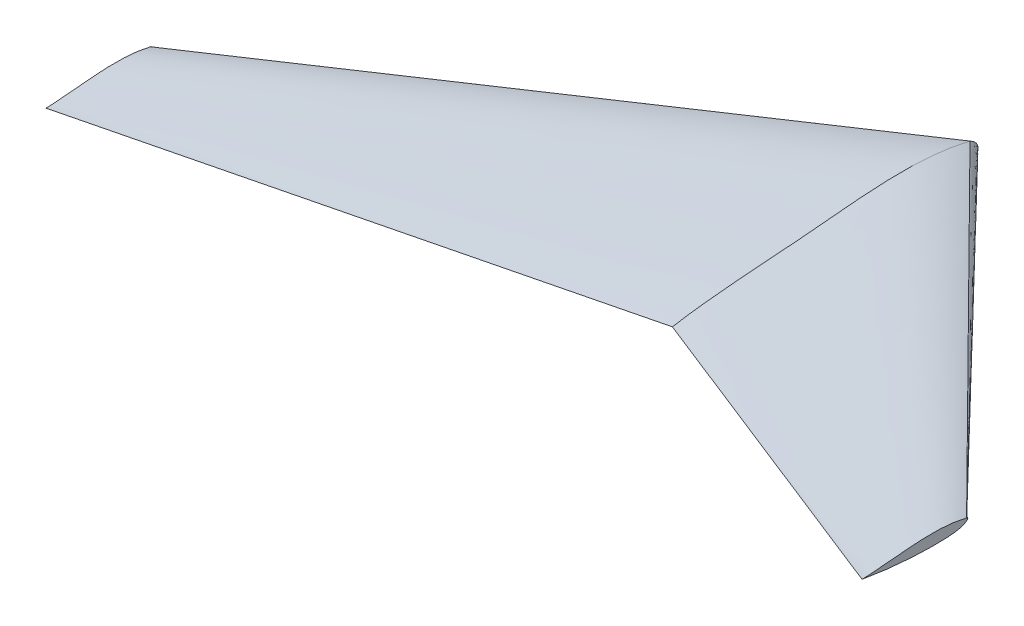
SolidWorks part; units mm, degrees
ref_plane "Front Plane" through (0, 0, 0) normal (0, 0, 1) x (1, 0, 0)
ref_plane "Top Plane" through (0, 0, 0) normal (0, 1, 0) x (1, 0, 0)
ref_plane "Right Plane" through (0, 0, 0) normal (1, 0, 0) x (0, 0, -1)
sketch "Sketch2" plane through (0, 0, 0) normal (0, 1, 0) x (1, 0, 0)
  line L0 (0, -6122.228) -> (0, 2040.7427)
  line L1 (0, 0) -> (-18096.1342, 0) construction
  line L2 (0, 0) -> (-21640.8, -16307.5125) construction
  line L3 (-21640.8, -18450.2946) -> (-21640.8, -15593.2518)
  line L4 (-21640.8, -15593.2518) -> (0, 2040.7427)
  line L5 (-21640.8, -18450.2946) -> (0, -6122.228)
  line L6 (-9083.802, -5361.1886) -> (-9083.802, -6845.1358) construction
  line L7 (-9083.802, -6845.1358) -> (-9083.802, -11296.9774) construction
  line L8 (-9083.802, -6845.1358) -> (0, -6845.1358) construction
  line L9 (0, 408.1485) -> (-18440.4, -13713.752)
  line L10 (0, -35661.6) -> (-6061.5652, -41119.4578) construction
  line L11 (0, -35661.6) -> (-8167.6786, -35661.6) construction
  line L12 (0, -34539.0879) -> (0, -39029.1363)
  line L13 (-6061.5652, -42298.0954) -> (-6061.5652, -40726.5786)
  line L14 (-6061.5652, -40726.5786) -> (0, -34539.0879)
  line L15 (0, -39029.1363) -> (-6061.5652, -42298.0954)
  line L16 (-2544.3607, -37136.3062) -> (-2544.3607, -37952.5526) construction
  line L17 (-2544.3607, -37952.5526) -> (-2544.3607, -40401.292) construction
  line L18 (-2544.3607, -37952.5526) -> (0, -37952.5526) construction
  line L19 (-18440.4, -13713.752) -> (-18440.4, -15898.787)
  line L20 (-18440.4, -15898.787) -> (0, -4489.6339)
  line L21 (0, 408.1485) -> (0, -4489.6339) construction
  line L22 (0, -4489.6339) -> (0, 408.1485) construction
  line L23 (0, 408.1485) -> (0, -2040.7427) construction
  line L24 (0, 408.1485) -> (0, -4489.6339) construction
  line L25 (0, -2040.7427) -> (-18440.4, -14806.2695) construction
  line L26 (0, 408.1485) -> (-21640.8, -16164.6603) construction
  line L27 (-6975.7046, -4933.9377) -> (-6975.7046, -6869.7347) construction
  line L28 (-6975.7046, -6869.7347) -> (-6975.7046, -8805.5317) construction
  line L29 (-6975.7046, -6869.7347) -> (0, -6869.7347) construction
  line L30 (-6061.5652, -41661.6311) -> (0, -37210.6667) construction
  dimension "Wing Sweep" = 37
  dimension "Half Span" = 21640.8
  dimension "Wing Root" = 8162.9707
  dimension "D4" = 2040.7427
  dimension "Wing Tip" = 2857.0428
  dimension "D6" = 714.2607
  dimension "Wing YBar" = 9083.802
  dimension "Tail Sweep" = 42
  dimension "Tail Root" = 4490.0484
  dimension "D10" = 1122.5121
  dimension "Tail Tip" = 1571.5168
  dimension "D12" = 392.8792
  dimension "D13" = 6061.5652
  dimension "Tail Ybar" = 2544.3607
  dimension "First Spar" = 1632.5941
  dimension "Second Spar" = 6530.3766
  dimension "Fuel Tip" = 2185.035
  dimension "Tip Spar" = 571.4086
  dimension "Fuel Ybar" = 6975.7046
  dimension "Fuel Tank Length" = 18440.4
  dimension "Tail Arm" = 35661.6
  dimension "D2" = 2671.5788
  dimension "D3" = 935.0525
sketch "Sketch4" plane through (0, 0, 0) normal (0, 1, 0) x (1, 0, 0)
  line L0 (0, 17538.8642) -> (0, -40677.9358) construction
  line L1 (-2194.56, 17538.8642) -> (2194.56, 17538.8642) construction
  line L2 (-2194.56, 10955.1842) -> (-2194.56, -31899.6958)
  line L3 (-2194.56, -40677.9358) -> (2194.56, -40677.9358) construction
  line L4 (2194.56, 10955.1842) -> (2194.56, -31899.6958)
  line L5 (0, -6122.228) -> (0, 2040.7427) construction
  line L6 (-9083.802, -6845.1358) -> (0, -6845.1358) construction
  line L7 (-2544.3607, -37952.5526) -> (0, -37952.5526) construction
  line L8 (0, 0) -> (-21640.8, -16307.5125) construction
  line L9 (-21640.8, -15593.2518) -> (0, 2040.7427) construction
  line L10 (-8474.964, 1555.5245) -> (-5807.964, 1555.5245)
  line L11 (-8474.964, 1555.5245) -> (-8474.964, -5453.2245)
  line L12 (-8474.964, -5453.2245) -> (-5807.964, -5453.2245)
  line L13 (-5807.964, 1555.5245) -> (-5807.964, -5453.2245)
  line L14 (2194.56, 10955.1842) -> (-2194.56, 10955.1842)
  arc A0 (-2194.56, -31899.6958) -> (2194.56, -31899.6958) centre (0, -31899.6958) ccw construction
  spline S0 degree 2 poles (-2194.56, 10955.1842) (-2319.3121, 14550.827) (0, 17538.8642) knots 0 0 0 1 1 1 construction
  spline S1 degree 2 poles (2194.56, 10955.1842) (2319.3121, 14550.827) (0, 17538.8642) knots 0 0 0 1 1 1 construction
  spline S2 degree 3 poles (-2194.56, -31899.6958) (-2185.0252, -17343.0176) (-1882.3736, -55849.4008) (-475.0937, -22625.7195) (0, -39029.1363) knots 0 0 0 0 0.566127 1 1 1 1 construction
  spline S3 degree 3 poles (2194.56, -31899.6958) (2185.0252, -17343.0176) (1882.3736, -55849.4008) (475.0937, -22625.7195) (0, -39029.1363) knots 0 0 0 0 0.566127 1 1 1 1 construction
  spline S4 degree 2 poles (-2194.56, -31899.6958) (-4104.2514, -24790.3016) (0, -27753.3552) knots 0 0 0 1 1 1
  spline S5 degree 2 poles (2194.56, -31899.6958) (4104.2514, -24790.3016) (0, -27753.3552) knots 0 0 0 1 1 1
  point P6 (0, 10955.1842)
  point P7 (0, -31899.6958)
  point P8 (0, -6845.1358)
  point P15 (0, -34094.2558)
  point P28 (-7141.464, 1555.5245)
  point P29 (-7141.464, -3778.4755)
  point P35 (-7141.464, -5381.4791)
  point P44 (-7141.464, -1247.9751)
  dimension "Fuse Length" = 58216.8
  dimension "Fuse Dia" = 4389.12
  dimension "D3" = 6583.68
  dimension "D4" = 8778.24
  dimension "D6" = 7141.464
  dimension "Engine Dia" = 2667
  dimension "Engine Length" = 7008.749
  dimension "D9" = 5334
  dimension "D10" = 2803.4996
  dimension "D11" = 5597.1607
  dimension "D2" = 24384
ref_plane "Plane1" through (0, 609.6, 0) normal (0, 1, 0) x (1, 0, 0)
sketch "Sketch10" plane through (0, 0, 0) normal (0, 1, 0) x (1, 0, 0)
  line L0 (-21640.8, -15593.2518) -> (-2194.56, 252.5066)
  line L1 (-2194.56, 10955.1842) -> (-2194.56, -31899.6958) construction
  line L2 (-21640.8, -15593.2518) -> (-21640.8, -18450.2946)
  line L3 (-21640.8, -18450.2946) -> (-7141.464, -10190.49)
  line L4 (-7141.464, -10190.49) -> (-2194.56, -10190.49)
  line L5 (-21640.8, -18450.2946) -> (0, -6122.228) construction
  line L6 (-21640.8, -15593.2518) -> (0, 2040.7427) construction
  line L7 (-2194.56, -10190.49) -> (-2194.56, 252.5066) construction
  line L9 (0, 271.2873) -> (0, -10190.49)
  line L10 (0, -10190.49) -> (-2194.56, -10190.49)
  line L11 (0, -6122.228) -> (0, 2040.7427) construction
  line L12 (-2194.56, 252.5066) -> (0, 2040.7427)
  line L13 (0, 2040.7427) -> (0, 271.2873)
ref_plane "Plane4" through (17265.894, 0, 16914.5049) normal (0.7143, 0, 0.6998) x (0.6998, 0, -0.7143)
ref_plane "Plane2" through (-6061.5652, 0, 0) normal (1, 0, 0) x (0, 0, -1)
sketch "Sketch11" plane through (0, 0, 0) normal (1, 0, 0) x (0, 0, -1)
  line L0 (-31394.1382, -352.4096) -> (-30857.4716, -352.4096) construction
  line L1 (-34539.0879, 0) -> (-39029.1363, 0) construction
  spline S0 degree 3 poles (-39051.8309, 0) (-38403.1581, 109.7274) (-36924.0487, 165.2873) (-35448.5779, 379.0643) (-34630.3278, 179.2815) knots 0 0 0 0 0.443797 1 1 1 1
  spline S1 degree 3 poles (-39051.8309, 0) (-38190.4109, -219.3036) (-37292.2896, -199.7787) (-36415.6545, -314.689) knots 0 0 0 0 1 1 1 1
  spline S2 degree 3 poles (-36415.6545, -314.689) (-35966.3296, -355.4965) (-35302.3779, -490.2862) (-34639.9796, -191.5367) (-34412.4231, 59.404) (-34630.3278, 179.2815) knots 0 0 0 0 0.638862 0.803347 1 1 1 1
sketch "Sketch12" plane through (17265.894, 0, 16914.5049) normal (0.7143, 0, 0.6998) x (0.6998, 0, -0.7143)
  line L0 (-24430.9437, -230.124) -> (-33334.4448, 1320.3427)
  line L1 (-24430.9437, 230.124) -> (-33334.4448, 1481.4295)
  line L2 (-24430.9437, 230.124) -> (-24430.9437, -230.124) construction
  line L3 (-33334.4448, 1481.4295) -> (-33334.4448, 1320.3427) construction
  line L4 (-24672.5966, 0) -> (-27880.0105, 0) construction
  line L5 (-33334.4448, 1481.4295) -> (-29601.6778, 1481.4295) construction
  point P1 (-24430.9437, 0)
  dimension "D2" = 460.248
  dimension "D1" = 161.0868
  dimension "D3" = 8
sketch "Sketch13" plane through (-6061.5652, 0, 0) normal (1, 0, 0) x (0, 0, -1)
  line L0 (-34331.3091, -72.3608) -> (-33794.6424, -72.3608) construction
  spline S0 degree 2 poles (-40724.5294, 1404.4596) (-40730.5109, 1415.5035) (-40742.886, 1417.5169) knots 0 0 0 1 1 1
  spline S1 degree 3 poles (-40724.5294, 1404.4596) (-40728.1705, 1391.3166) (-40749.7129, 1371.5832) (-40803.3426, 1344.4219) (-40887.0623, 1323.8384) (-41020.1248, 1308.2966) (-41187.7751, 1304.7034) (-41622.8293, 1310.9853) (-41993.7888, 1351.6044) (-42295.2916, 1404.0762) knots 0 0 0 0 0.024793 0.052363 0.112618 0.184636 0.303441 0.426297 1 1 1 1
  spline S2 degree 3 poles (-42295.2916, 1404.0762) (-42240.4101, 1402.9617) (-42146.1609, 1412.2938) (-41981.2937, 1426.3091) (-41779.6693, 1442.2613) (-41356.9291, 1482.4133) (-41001.1814, 1481.6374) (-40742.886, 1417.5169) knots 0 0 0 0 0.105305 0.182318 0.318577 0.494689 1 1 1 1
loft "Loft1" add profiles "Sketch13", "Sketch11" connector at (-6061.5652, 1404.0762, 42295.2916) connector at (0, 0, 39051.8309)
mirror "Mirror1" about plane through (0, 0, 0) normal (1, 0, 0) of bodies 130
equation "\"D6@Sketch2\" = \"Wing Tip@Sketch2\" / 4"
equation "\"D4@Sketch2\" = \"Wing Root@Sketch2\" / 4"
equation "\"D10@Sketch2\" = \"Tail Root@Sketch2\" / 4"
equation "\"D12@Sketch2\" = \"Tail Tip@Sketch2\" / 4"
equation "\"D13@Sketch2\"=39.77405/2"
equation "\"First Spar@Sketch2\"=0.2 * \"Wing Root@Sketch2\""
equation "\"Second Spar@Sketch2\" = 0.8 * \"Wing Root@Sketch2\""
equation "\"Tip Spar@Sketch2\"=0.2 * \"Wing Tip@Sketch2\""
equation "\"D3@Sketch4\" = 1.5 * \"Fuse Dia@Sketch4\""
equation "\"D4@Sketch4\" = 2 * \"Fuse Dia@Sketch4\""
equation "\"D6@Sketch4\" = 0.33 * \"Half Span@Sketch2\""
equation "\"D9@Sketch4\" = 2 * \"Engine Dia@Sketch4\""
equation "\"D10@Sketch4\" = 0.40 * \"Engine Length@Sketch4\""
equation "\"D1@Sketch12\"=0.35*\"D2@Sketch12\""
equation "\"D2@Sketch2\"=0.595*\"Tail Root@Sketch2\""
equation "\"D3@Sketch2\"=.595*\"Tail Tip@Sketch2\""
